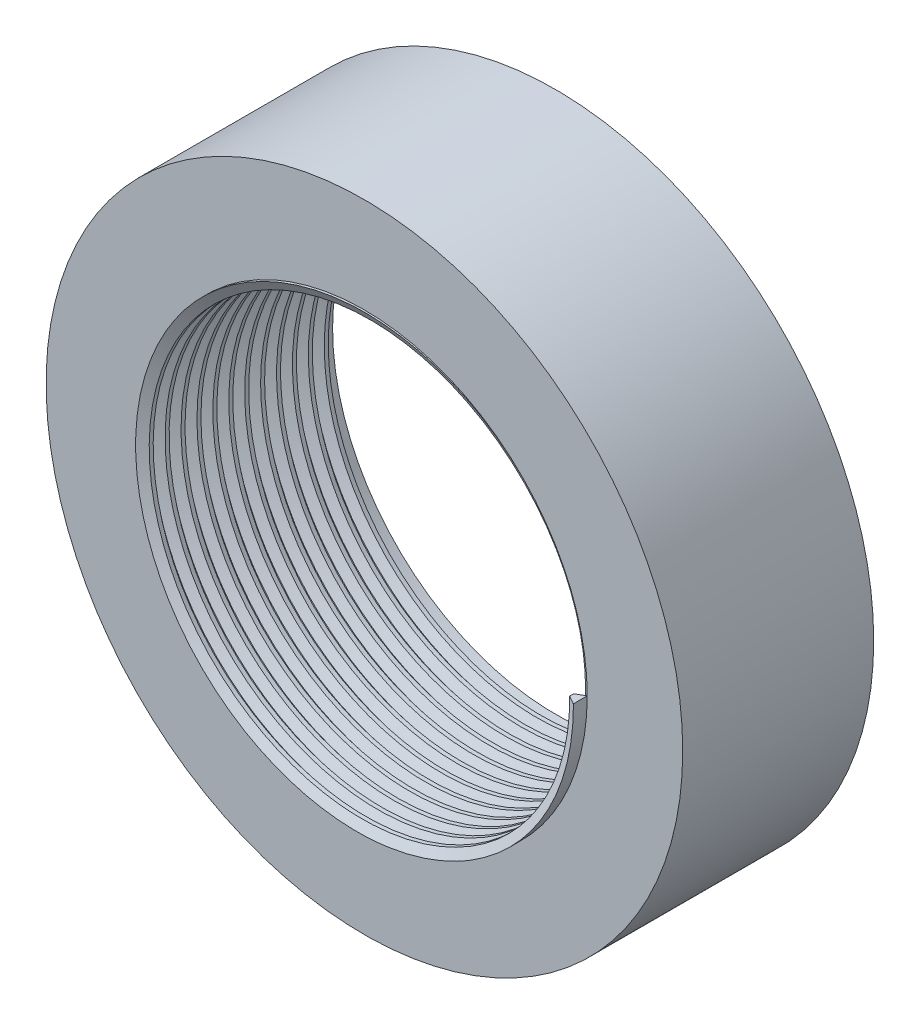
SolidWorks part; units mm, degrees
ref_plane "Front Plane" through (0, 0, 0) normal (0, 0, 1) x (1, 0, 0)
ref_plane "Top Plane" through (0, 0, 0) normal (0, 1, 0) x (1, 0, 0)
ref_plane "Right Plane" through (0, 0, 0) normal (1, 0, 0) x (0, 0, -1)
sketch "Sketch1" plane through (0, 0, 0) normal (0, 0, 1) x (1, 0, 0)
  circle A0 centre (0, 0) radius 5
  circle A1 centre (0, 0) radius 3.5
  dimension "D1" = 10
  dimension "D2" = 7
extrude "Boss-Extrude1" add sketch "Sketch1" along normal blind 3
thread "Thread1" pitch 0.25 method extrude profile "Thread Profile1" start angle 0, offset 0, length 3, pitch 0.25, diameter 7
ref_plane "Plane1" through (3.5, 0, 0) normal (0, -1, 0) x (1, 0, 0)
sketch "Thread Profile1" plane through (3.5, 0, 0) normal (0, -1, 0) x (1, 0, 0)
  line L0 (0, 0) -> (0, 0.25) construction
  line L11 (0, 0) -> (0, 0.2187)
  line L12 (0, 0.2187) -> (-0.1353, 0.1406)
  line L13 (-0.1353, 0.1406) -> (-0.1353, 0.0781)
  line L15 (-0.1353, 0.0781) -> (0, 0)
  line L17 (-0.1353, 0.1094) -> (0, 0.1094) construction
  point P2 (0, 0)
  dimension "Pitch" = 0.25
  dimension "Profile_Angle" = 60
  dimension "Profile_Land" = 0.0625
  dimension "Profile_Height" = 0.1353
